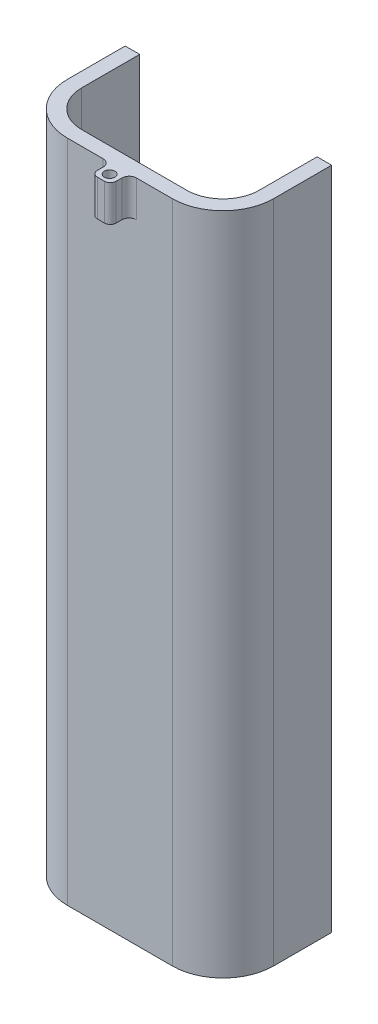
SolidWorks part; units mm, degrees
ref_plane "Front Plane" through (0, 0, 0) normal (0, 0, 1) x (1, 0, 0)
ref_plane "Top Plane" through (0, 0, 0) normal (0, 1, 0) x (1, 0, 0)
ref_plane "Right Plane" through (0, 0, 0) normal (1, 0, 0) x (0, 0, -1)
sketch "Sketch1" plane through (0, 0, 0) normal (0, 0, 1) x (1, 0, 0)
  line L0 (-10.5, 67.5) -> (-22.5, 67.5) construction
  line L1 (-10.5, 67.5) -> (-10.5, -67.5) construction
  line L2 (-22.5, -67.5) -> (-10.5, -67.5) construction
  line L3 (10.5, 67.5) -> (-10.5, 67.5) construction
  line L4 (-10.5, -67.5) -> (10.5, -67.5) construction
  line L5 (22.5, 67.5) -> (10.5, 67.5) construction
  line L6 (10.5, -67.5) -> (22.5, -67.5) construction
  line L7 (10.5, -67.5) -> (10.5, 67.5) construction
  line L8 (-10.5, 67.5) -> (-22.5, 67.5)
  line L9 (-10.5, 67.5) -> (-10.5, -67.5)
  line L10 (-22.5, -67.5) -> (-10.5, -67.5)
  line L11 (10.5, 67.5) -> (-10.5, 67.5)
  line L12 (-10.5, -67.5) -> (10.5, -67.5)
  line L13 (22.5, 67.5) -> (10.5, 67.5)
  line L14 (10.5, -67.5) -> (22.5, -67.5)
  line L15 (10.5, -67.5) -> (10.5, 67.5)
  line L16 (-28.5, 110) -> (-28.5, -73.5)
  line L17 (-24.5, 106) -> (24.5, 106)
  line L18 (-24.5, 106) -> (-24.5, -69.5)
  line L19 (-24.5, -69.5) -> (24.5, -69.5)
  line L20 (24.5, 106) -> (24.5, -69.5)
  line L21 (-28.5, -73.5) -> (28.5, -73.5)
  line L22 (28.5, 110) -> (28.5, -73.5)
  line L23 (-28.5, 110) -> (28.5, 110)
  circle A0 centre (0, 90) radius 10 construction
  dimension "D4" = 16
  dimension "D1" = 2
  dimension "D2" = 2
  dimension "D3" = 2
  dimension "D5" = 4
extrude "Boss-Extrude1" add sketch "Sketch1" along normal offset from surface (30 mm away) 6 contours L23 L16 L21 L22 L17 L20 L19 L18 region at (0, 108.0785, 0) offset beyond the face yes
sketch "Sketch2" plane through (0, -69.5, 0) normal (0, 1, 0) x (1, 0, 0)
  line L0 (-24.5, -30) -> (-24.5, 0) construction
  line L1 (24.5, -30) -> (-24.5, -30)
  line L2 (24.5, -30) -> (24.5, -26)
  line L3 (24.5, -26) -> (-24.5, -26)
  line L4 (-24.5, -30) -> (-24.5, -26)
  line L5 (24.5, -30) -> (24.5, 0) construction
  line L6 (24.5, -16) -> (24.5, -26)
  line L7 (-24.5, -16) -> (-24.5, -26)
  line L8 (24.5, -16) -> (24.5, 0)
  line L9 (24.5, 0) -> (-24.5, 0)
  line L10 (-24.5, 0) -> (-24.5, -16)
  arc A0 (24.5, -16) -> (14.5, -26) centre (14.5, -16) cw
  arc A1 (-14.5, -26) -> (-24.5, -16) centre (-14.5, -16) cw
  line M5 (-24.5, -30) -> (24.5, -30)
  line M6 (24.5, -30) -> (24.5, 0)
  line M7 (24.5, 0) -> (-24.5, 0)
  line M8 (-24.5, 0) -> (-24.5, -30)
  dimension "D2" = 10
  dimension "D3" = 10
  dimension "D1" = 4
extrude "Boss-Extrude2" add sketch "Sketch2" along normal up to surface (175.5 mm away) contours A0 L3 M6 | L3 M6 M8 M5 | L3 A1 M8 region at (0, -69.5, 28) region at (22.2663, -69.5, 23.7663) region at (-22.2663, -69.5, 23.7663) up to face at (0, 106, 15)
fillet "Fillet1" radius 14 2 edges at (28.5, 18.25, 30) (-28.5, 18.25, 30)
extrude "Cut-Extrude1" cut sketch "Sketch2<4>" along normal up to surface (179.5 mm away) contours A1 L3 A0 M6 M7 M8 region at (0, -69.5, 12.6246) up to face at (0, 110, 16.2998)
sketch "Sketch2<4>" plane through (0, -69.5, 0) normal (0, 1, 0) x (1, 0, 0) same geometry as "Sketch2"
sketch "Sketch6" plane through (0, 110, 0) normal (0, 1, 0) x (1, 0, 0)
  line L0 (-2.6, -32.8) -> (2.6, -32.8) construction
  line L1 (0, -35.2) -> (0, -32.8) construction
  line L3 (2.6, -33.6) -> (2.6, -32)
  line L4 (-1, -35.2) -> (1, -35.2)
  line L5 (-2.6, -33.6) -> (-2.6, -32)
  line L6 (-4.6, -30) -> (4.6, -30)
  line L7 (14.5, -30) -> (-14.5, -30) construction
  line L8 (14.5, -30) -> (-14.5, -30)
  circle A5 centre (0, -32.8) radius 1.6
  arc A6 (4.6, -30) -> (2.6, -32) centre (4.6, -32) ccw
  arc A7 (1, -35.2) -> (2.6, -33.6) centre (1, -33.6) ccw
  arc A8 (-2.6, -33.6) -> (-1, -35.2) centre (-1, -33.6) ccw
  arc A9 (-2.6, -32) -> (-4.6, -30) centre (-4.6, -32) ccw
  circle A10 centre (0, -32.8) radius 1.45
  point P14 (0, -30)
  point P15 (0, -30)
  line M10 (-14.5, -30) -> (14.5, -30)
  dimension "D1" = 2.9
  dimension "D2" = 2
  dimension "D3" = 2
  dimension "D5" = 3.2
  dimension "D6" = 1.6
  dimension "D7" = 1.6
  dimension "D4" = 9.2
  dimension "D8" = 2
  dimension "D9" = 1.6
  dimension "D10" = 1.6
extrude "Boss-Extrude5" add sketch "Sketch6" against normal blind 10 contours A9 L5 A8 L4 A7 L3 A6 A5 M10 | A5 A10 region at (2.0566, 110, 34.6566) region at (-1.5547, 110, 32.8)
